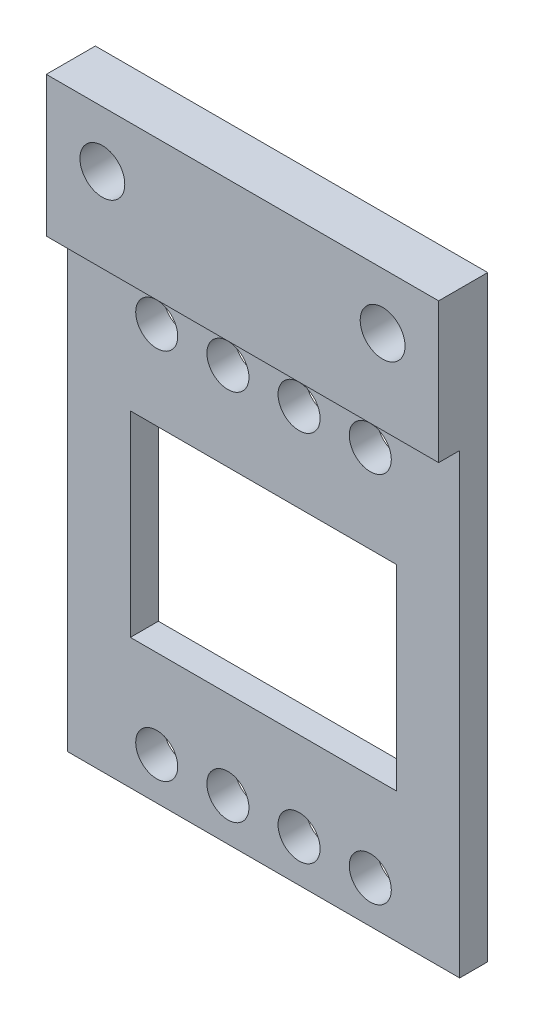
SolidWorks part; units mm, degrees
note: The reader was unsure of these and kept them because the rebuilt part matched: shared geometry of "Sketch1<7>", "Sketch1<9>".
ref_plane "Front Plane" through (0, 0, 0) normal (0, 0, 1) x (1, 0, 0)
ref_plane "Top Plane" through (0, 0, 0) normal (0, 1, 0) x (1, 0, 0)
ref_plane "Right Plane" through (0, 0, 0) normal (1, 0, 0) x (0, 0, -1)
sketch "Sketch1" plane through (0, 0, 0) normal (0, 0, 1) x (1, 0, 0)
  line L0 (-12.9214, 0) -> (9.9938, 0) construction
  line L1 (-5, 6.65) -> (5, 6.65)
  line L2 (-5, 6.65) -> (-5, -6.65)
  line L3 (-5, -6.65) -> (5, -6.65)
  line L4 (5, 6.65) -> (5, -6.65)
  line L5 (-5, 6.65) -> (5, -6.65) construction
  line L6 (-5, -6.65) -> (5, 6.65) construction
  line L7 (-7, 8.15) -> (7, 8.15)
  line L8 (-7, 8.15) -> (-7, -8.15)
  line L9 (-7, -8.15) -> (7, -8.15)
  line L10 (7, 8.15) -> (7, -8.15)
  line L11 (-7, 8.15) -> (7, -8.15) construction
  line L12 (-7, -8.15) -> (7, 8.15) construction
  line L13 (0, -10.8255) -> (0, 8.0345) construction
  line L14 (-3.81, -6.65) -> (3.81, -6.65) construction
  line L15 (7, -8.15) -> (7, 8.15)
  line L16 (7, -8.15) -> (12, -8.15)
  line L17 (-4.75, 3.5) -> (4.75, 3.5)
  line L18 (-4.75, 3.5) -> (-4.75, -3.5)
  line L19 (-4.75, -3.5) -> (4.75, -3.5)
  line L20 (4.75, 3.5) -> (4.75, -3.5)
  line L21 (-4.75, 3.5) -> (4.75, -3.5) construction
  line L22 (-4.75, -3.5) -> (4.75, 3.5) construction
  line L23 (7, 8.15) -> (12, 8.15)
  line L24 (12, -8.15) -> (12, 8.15)
  line L25 (7, 8.15) -> (-7, 8.15)
  line L26 (7, 8.15) -> (7, 13.15)
  line L27 (-7, 8.15) -> (-7, 13.15)
  line L28 (7, 13.15) -> (-7, 13.15)
  point P0 (0, 0)
  point P1 (0, 0)
  point P13 (-3.81, -6.65)
  point P18 (-1.27, -6.65)
  point P19 (1.27, -6.65)
  point P20 (3.81, -6.65)
  point P21 (-5.5, 5)
  point P22 (0, -6.65)
  point P23 (5.5, 5)
  point P24 (3.81, 6.65)
  point P25 (1.27, 6.65)
  point P26 (-1.27, 6.65)
  point P27 (-3.81, 6.65)
  point P28 (5, 11.15)
  point P29 (10, -5)
  point P30 (-5.5, -5)
  point P31 (5.5, -5)
  point P34 (0, 0)
  point P39 (-5, 11.15)
  point P45 (10, 5)
  dimension "D1" = 13.3
  dimension "D2" = 10
  dimension "D3" = 14
  dimension "D4" = 16.3
  dimension "D6" = 7
  dimension "D7" = 9.5
  dimension "D8" = 1.5
  dimension "D9" = 1.5
  dimension "D10" = 5
  dimension "D11" = 2
  dimension "D12" = 5
  dimension "D13" = 5
  dimension "D14" = 2
  dimension "D15" = 5
  dimension "D5" = 4
extrude "cap_extrude" add sketch "Sketch1" along normal blind 1 contours L10 L7 L8 L9 L1 L4 L3 L2 | L4 L1 L2 L3 L17 L20 L19 L18 | L20 L17 L18 L19
shell "cap_shell-out" [suppressed] thickness 0.5
extrude "flap_extrude" add sketch "Sketch1<7>" along normal blind 1.75 contours L25 L26 L28 L27
sketch "Sketch1<7>" plane through (0, 0, 0) normal (0, 0, 1) x (1, 0, 0) same geometry as "Sketch1"
hole_wizard "M2 Clearance Hole1" [suppressed] positions "Sketch18" profile "Sketch19" hole size "M2" standard "ISO"
sketch "Sketch18" [suppressed] plane through (0, 0, 1.5) normal (0, 0, 1) x (1, 0, 0)
  point P8 (-5, 11.15)
  point P11 (5, 11.15)
sketch "Sketch19" plane through (-5, 11.15, 1.5) normal (1, 0, 0) x (0, -1, 0)
  line L0 (0, 0) -> (0, 1.5)
  line L1 (0, 1.5) -> (1.2, 1.5)
  line L2 (1.2, 1.5) -> (1.2, 0)
  line L5 (1.2, 0) -> (0, 0)
  line L11 (0, -6.35) -> (0, 107.95) construction
  dimension "Thru Hole Dia." = 2.4
  dimension "Thru Hole Depth" = 1.5
extrude "Cut-Extrude2" cut sketch "Sketch1<9>" along normal up to next contours L20 L17 L18 L19
sketch "Sketch1<9>" plane through (0, 0, 0) normal (0, 0, 1) x (1, 0, 0) same geometry as "Sketch1"
hole_wizard "Ø1.5mm Dowel Hole1" positions "Sketch11" profile "Sketch12" hole size "Ø1.5" standard "ISO" end condition up to next
sketch "Sketch11" plane through (0, 0, 0) normal (0, 0, -1) x (-1, 0, 0)
  point P0 (3.81, 6.65)
  point P3 (1.27, 6.65)
  point P6 (-1.27, 6.65)
  point P9 (-3.81, 6.65)
  point P12 (-3.81, -6.65)
  point P15 (-1.27, -6.65)
  point P18 (1.27, -6.65)
  point P21 (3.81, -6.65)
sketch "Sketch12" plane through (-3.81, 6.65, 0) normal (1, 0, 0) x (0, 1, 0)
  line L0 (0, 0) -> (0, 1)
  line L1 (0, 1) -> (0.75, 1)
  line L2 (0.75, 1) -> (0.75, 0)
  line L5 (0.75, 0) -> (0, 0)
  line L11 (0, -6.35) -> (0, 107.95) construction
  dimension "Thru Hole Dia." = 1.5
  dimension "Thru Hole Depth" = 1
sketch "Sketch15" [suppressed] plane through (0, 0, 0.75) normal (0, 0, 1) x (1, 0, 0)
  line L4 (-4, -2.75) -> (4, -2.75)
  line L6 (-4, -2.75) -> (4, -2.75)
  line L12 (4, -2.75) -> (4, 2.75)
  line L13 (4, -2.75) -> (4, 2.75)
  line L14 (4, 2.75) -> (-4, 2.75)
  line L16 (4, 2.75) -> (-4, 2.75)
  line L18 (-4, 2.75) -> (-4, -2.75)
  line L20 (-4, 2.75) -> (-4, -2.75)
  dimension "D1" = 0
hole_wizard "Tap Drill for M2 Tap1" positions "Sketch22" profile "Sketch23" hole size "M2" standard "ISO" end condition up to next
sketch "Sketch22" plane through (0, 0, 0) normal (0, 0, -1) x (-1, 0, 0)
  point P0 (-5, 11.15)
  point P3 (5, 11.15)
sketch "Sketch23" plane through (5, 11.15, 0) normal (1, 0, 0) x (0, 1, 0)
  line L0 (0, 0) -> (0, 1.75)
  line L1 (0, 1.75) -> (0.8, 1.75)
  line L2 (0.8, 1.75) -> (0.8, 0)
  line L5 (0.8, 0) -> (0, 0)
  line L11 (0, -6.35) -> (0, 107.95) construction
  dimension "Thru Hole Dia." = 1.6
  dimension "Thru Hole Depth" = 1.75
sketch "Sketch24" [suppressed] plane through (0, 13.15, 0) normal (0, 1, 0) x (1, 0, 0)
  line L0 (7, 0) -> (-7, 0) construction
  line L1 (0, -6.743) -> (0, 6.743) construction
  point P0 (0, 0)
  dimension "D1" = 0
hole_wizard "Ø2.0mm Dowel Hole1" [suppressed] positions "Sketch25" profile "Sketch26" hole size "Ø2.0" standard "ISO"
sketch "Sketch25" plane through (0, 13.15, 0) normal (0, 1, 0) x (1, 0, 0)
  point P0 (0, 0)
sketch "Sketch26" plane through (0, 13.15, 0) normal (1, 0, 0) x (0, 0, 1)
  line L0 (0, 0) -> (0, 5.5)
  line L1 (0, 5.5) -> (1, 5.5)
  line L2 (1, 5.5) -> (1, 0)
  line L5 (1, 0) -> (0, 0)
  line L11 (0, -6.35) -> (0, 107.95) construction
  dimension "Thru Hole Dia." = 2
  dimension "Thru Hole Depth" = 5.5
equation "\"D3@Sketch1\"=\"D2@Sketch1\"+4"
equation "\"D4@Sketch1\"=\"D1@Sketch1\"+3"
equation "\"D7@Sketch1\"=\"D2@Sketch1\"-0.5"
